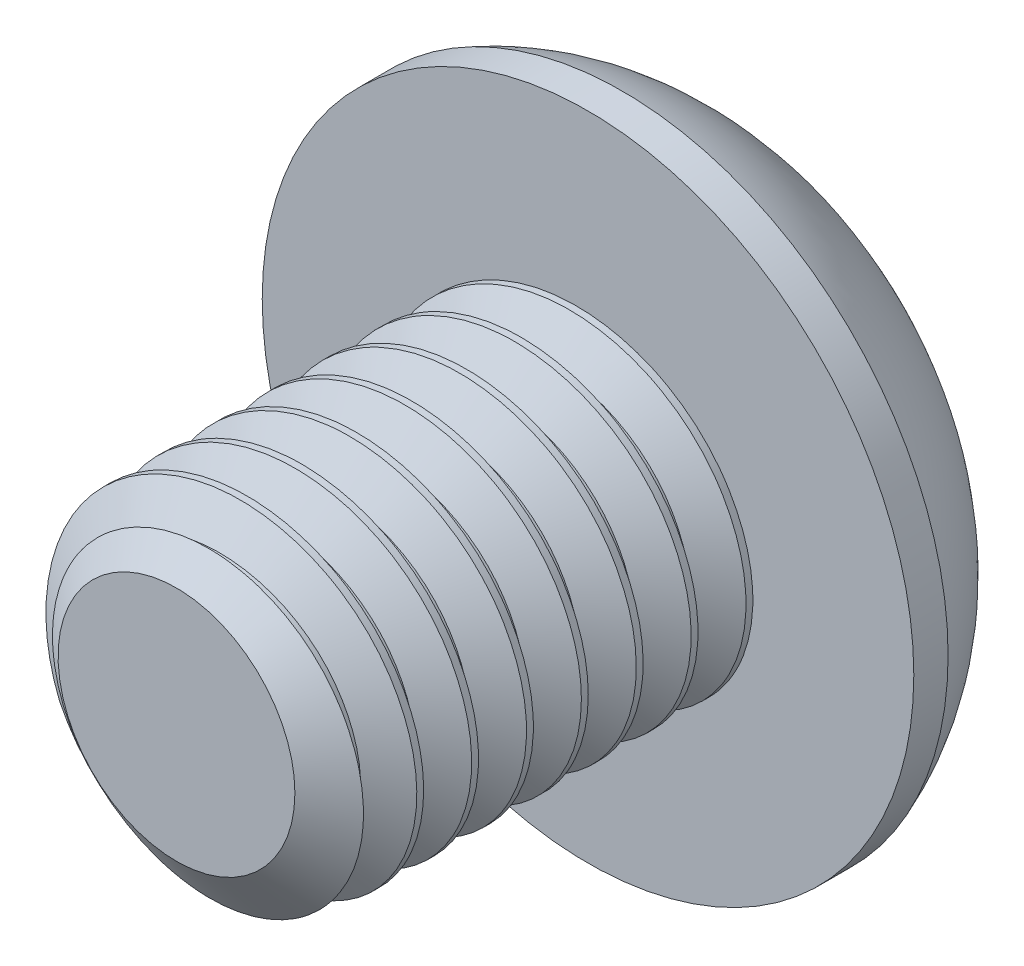
SolidWorks part; units mm, degrees
material "Alloy Steel"
ref_plane "Front Plane" through (0, 0, 0) normal (0, 0, 1) x (1, 0, 0)
ref_plane "Top Plane" through (0, 0, 0) normal (0, 1, 0) x (1, 0, 0)
ref_plane "Right Plane" through (0, 0, 0) normal (1, 0, 0) x (0, 0, -1)
sketch "Sketch1" plane through (0, 0, 0) normal (0, 0, 1) x (1, 0, 0)
  circle A0 centre (0, 0) radius 2.5
  dimension "OD" = 5
extrude "Extrude1" add sketch "Sketch1" against normal blind 6
sketch "Sketch2" plane through (0, 0, 0) normal (0, 0, 1) x (1, 0, 0)
  circle A0 centre (0, 0) radius 2.5 construction
  circle A1 centre (0, 0) radius 2.5
curve "Helix/Spiral1" pitch 0.8 height 6.8 turns 8.5 parameters "pitch"=0.8
sketch "Sketch3" plane through (0, 0, 0) normal (1, 0, 0) x (0, 0, -1)
  line L0 (-0.7, 2.5) -> (-0.4, 1.9804)
  line L1 (-0.4, 1.9804) -> (-0.3, 1.9804)
  line L2 (-0.3, 1.9804) -> (0, 2.5)
  line L3 (-0.7, 2.5) -> (0, 2.5)
  line L4 (-0.35, 2.5) -> (-0.35, 1.9804) construction
  line L5 (-0.55, 2.2402) -> (-0.15, 2.2402) construction
  line L6 (0, 2.5) -> (0, -2.5) construction
  dimension "D1" = 0.1
  dimension "D2" = 0.4
  dimension "D3" = 60
sweep "Cut-Sweep1" cut profiles "Sketch3" path "Helix/Spiral1"
sketch "Sketch4" plane through (0, 0, 0) normal (1, 0, 0) x (0, 0, -1)
  line L0 (0.5417, 2.5) -> (0, 1.7264)
  line L1 (0, 1.7264) -> (0, 2.5)
  line L2 (0.5417, 2.5) -> (0, 2.5)
  line L3 (-0.7, 2.5) -> (0, 2.5) construction
  line L4 (0, 0) -> (7.0209, 0) construction
  dimension "D1" = 55
  dimension "D2" = 0.254
revolve "Cut-Revolve1" cut sketch "Sketch4" angle 360 about L4
sketch "Sketch5" plane through (0, 0, 0) normal (1, 0, 0) x (0, 0, -1)
  line L0 (6, -1.7838) -> (6, 1.991) construction
  line L1 (6, 2.627) -> (28.1202, 2.627)
  line L2 (6, 2.627) -> (6, 0)
  line L3 (6, 0) -> (28, 0)
  line L4 (28, 2.2968) -> (28, 0)
  line L5 (28.1202, 2.627) -> (28, 2.2968)
  line L6 (0, 0) -> (9.9695, 0) construction
  point P3 (28, 2.627)
  point P10 (28, 2.627)
  dimension "D1" = 0.3302
  dimension "Thread min" = 28
  dimension "D2" = 0.127
  dimension "D3" = 20
revolve "partially thread" [suppressed] add sketch "Sketch5" angle 360 about L6
sketch "Sketch6" plane through (0, 0, -6) normal (0, 0, -1) x (-1, 0, 0)
  circle A0 centre (0, 0) radius 4.75
  dimension "head dia" = 9.5
extrude "Extrude2" add sketch "Sketch6" along normal blind 2.75
sketch "Sketch10" plane through (0, 0, 0) normal (1, 0, 0) x (0, 0, -1)
  line L0 (8.75, -4.75) -> (8.75, 4.75) construction
  line L1 (0, 0) -> (15.9584, 0) construction
  line L2 (8.75, 4.75) -> (6, 4.75) construction
  line L3 (6, 4.75) -> (6, -4.75) construction
  line L4 (6.5, 4.75) -> (6.5, 5.25)
  line L5 (6.5, 5.25) -> (9.25, 5.25)
  line L6 (9.25, 5.25) -> (9.25, 1.5)
  line L7 (8.75, 1.5) -> (9.25, 1.5)
  arc A0 (8.75, 1.5) -> (6.5, 4.75) centre (5.2778, 1.5) ccw
  dimension "D1" = 3
  dimension "D2" = 0.5
  dimension "D3" = 0.5
revolve "Cut-Revolve2" cut sketch "Sketch10" angle 360 about L1
ref_plane "Plane1" through (0, 0, -8.75) normal (0, 0, 1) x (1, 0, 0)
sketch "Sketch7" plane through (0, 0, -8.75) normal (0, 0, -1) x (-1, 0, 0)
  line L1 (0, 1.7321) -> (-1.5, 0.866)
  line L2 (-1.5, 0.866) -> (-1.5, -0.866)
  line L3 (-1.5, -0.866) -> (0, -1.7321)
  line L4 (0, -1.7321) -> (1.5, -0.866)
  line L5 (1.5, -0.866) -> (1.5, 0.866)
  line L6 (1.5, 0.866) -> (0, 1.7321)
  circle A0 centre (0, 0) radius 1.5 construction
  dimension "hex dia" = 3
extrude "Cut-Extrude1" cut sketch "Sketch7" against normal blind 2.25
sketch "Sketch8" plane through (0, 0, -8.75) normal (0, 0, 1) x (1, 0, 0)
  circle A0 centre (0, 0) radius 1.7321
extrude "Cut-Extrude2" cut sketch "Sketch8" along normal through all draft 45
sketch "Sketch9" plane through (0, 0, 0) normal (1, 0, 0) x (0, 0, -1)
  line L0 (0, 2.5) -> (0, -2.5) construction
  line L1 (4.4, 2.5) -> (4.4, -2.5) construction
  dimension "D1" = 4.4
equation "\"D3@Helix/Spiral1\" = \"screw length@Extrude1\"+\"pitch@Helix/Spiral1\""
equation "\"D1@Sketch3\" = \"pitch@Helix/Spiral1\"*.125"
equation "\"D2@Sketch3\" = \"pitch@Helix/Spiral1\"*.5"
equation "\"D1@Cut-Extrude1\" = \"hex dia@Sketch7\"*.75"
equation "\"D1@Sketch9\" = \"pitch@Helix/Spiral1\"*5.5"
equation "\"D1@Sketch10\" = \"hex dia@Sketch7\""
equation "\"D1@Plane1\" = \"head depth@Extrude2\""
